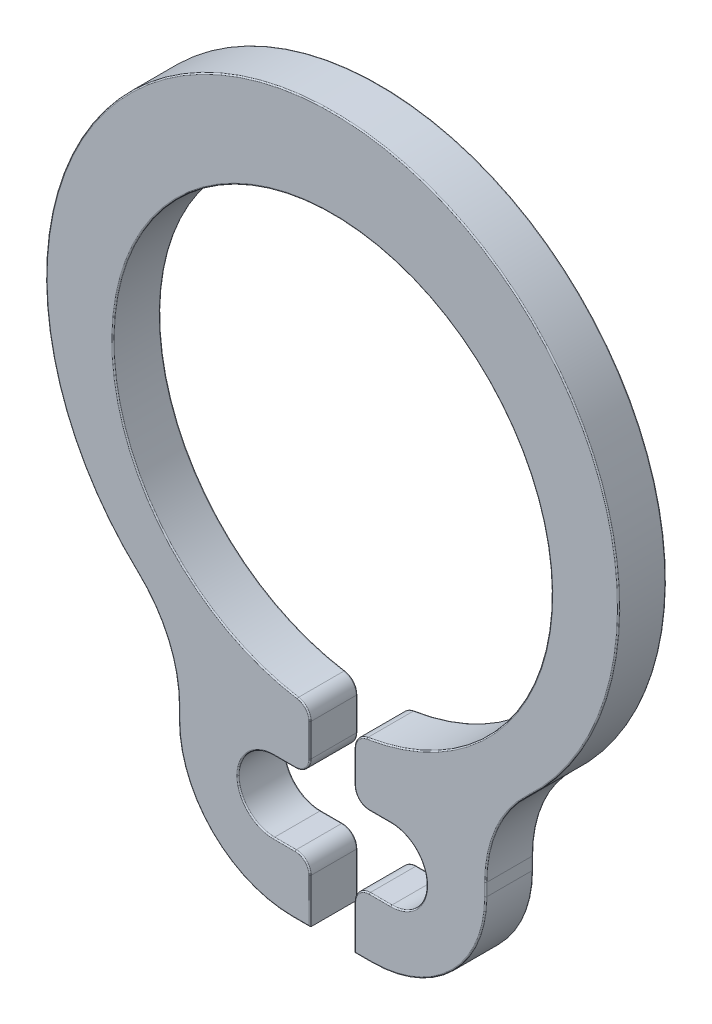
SolidWorks part; units mm, degrees
ref_plane "Front Plane" through (0, 0, 0) normal (0, 0, 1) x (1, 0, 0)
ref_plane "Top Plane" through (0, 0, 0) normal (0, 1, 0) x (1, 0, 0)
ref_plane "Right Plane" through (0, 0, 0) normal (1, 0, 0) x (0, 0, -1)
sketch "Sketch1" plane through (0, 0, 0) normal (0, 0, 1) x (1, 0, 0)
  line L0 (0, 6.05) -> (0, -6.05) construction
  line L1 (-0.99, -4.45) -> (0.99, -4.45) construction
  line L2 (-0.99, -3.85) -> (0.99, -3.85)
  line L3 (-0.99, -5.05) -> (0.99, -5.05)
  line L4 (1.59, -4.45) -> (2.59, -4.45) construction
  line L5 (0, -2.85) -> (0, -3.85) construction
  circle A0 centre (0, 0.85) radius 3.7
  arc A3 (-0.99, -3.85) -> (-0.99, -5.05) centre (-0.99, -4.45) ccw
  arc A4 (0.99, -5.05) -> (0.99, -3.85) centre (0.99, -4.45) ccw
  circle A5 centre (0, 1.22) radius 4.83 construction
  circle A6 centre (0, 0.85) radius 4 construction
  circle A7 centre (0, 0.85) radius 3.8 construction
  point P6 (0, 4.55)
  point P7 (0, -2.85)
  point P10 (0, -4.45)
  dimension "For OD" = 8
  dimension "ID" = 7.4
  dimension "Band Width" = 1.5
  dimension "Tap Height" = 3.2
  dimension "Tap ID" = 1.2
  dimension "D3" = 1.6
  dimension "Tap Width Ref" = 5.18
  dimension "D1" = 0.37
sketch "Sketch2" plane through (0, 0, 0) normal (1, 0, 0) x (0, 0, -1)
  line L0 (-0.4, 6.05) -> (0.4, 6.05) construction
  line L1 (0, 7.75) -> (0, -6.05) construction
  line L2 (0, 6.05) -> (0, -6.05) construction
  line L3 (-0.45, 7.75) -> (0.45, 7.75) construction
  line L4 (-0.45, -6.05) -> (0.45, -6.05) construction
  dimension "Thickness" = 0.8
  dimension "For Groove Width" = 0.9
sketch "Sketch3" plane through (0, 0, 0) normal (0, 0, 1) x (1, 0, 0)
  line L0 (-0.99, -5.05) -> (0.99, -5.05) construction
  line L1 (-0.99, -3.85) -> (0.99, -3.85) construction
  line L2 (-0.99, -5.05) -> (0.99, -5.05)
  line L3 (-0.99, -3.85) -> (0.99, -3.85)
  line L4 (2.59, -3.9186) -> (2.59, -4.13)
  line L5 (-0.67, -6.05) -> (0.67, -6.05)
  line L6 (-2.59, -3.9186) -> (-2.59, -4.13)
  line L7 (-1.59, -4.45) -> (-2.59, -4.45) construction
  line L8 (1.59, -4.45) -> (2.59, -4.45) construction
  arc A0 (-0.99, -3.85) -> (-0.99, -5.05) centre (-0.99, -4.45) ccw construction
  arc A1 (0.99, -5.05) -> (0.99, -3.85) centre (0.99, -4.45) ccw construction
  arc A2 (-0.99, -3.85) -> (-0.99, -5.05) centre (-0.99, -4.45) ccw
  arc A3 (0.99, -5.05) -> (0.99, -3.85) centre (0.99, -4.45) ccw
  circle A4 centre (0, 0.85) radius 3.7 construction
  circle A5 centre (0, 0.85) radius 3.7
  arc A6 (-3.2875, -2.3186) -> (3.2875, -2.3186) centre (0, 1.22) cw
  arc A8 (3.2875, -2.3186) -> (2.59, -3.9186) centre (4.7739, -3.9186) ccw
  arc A9 (2.59, -4.13) -> (0.67, -6.05) centre (0.67, -4.13) cw
  arc A10 (-3.2875, -2.3186) -> (-2.59, -3.9186) centre (-4.7739, -3.9186) cw
  arc A11 (-2.59, -4.13) -> (-0.67, -6.05) centre (-0.67, -4.13) ccw
  circle A12 centre (0, 1.22) radius 4.83 construction
  dimension "D1" = 1.6
  dimension "D2" = 1.92
  dimension "D3" = 1
extrude "Boss-Extrude1" add sketch "Sketch3" along normal mid plane 0.8
sketch "Sketch4" plane through (0, 0, 0) normal (0, 0, 1) x (1, 0, 0)
  line L0 (0, 0.85) -> (0, -6.05)
extrude "Cut-Extrude-Thin1" cut sketch "Sketch4" against normal through all both and the other way through all thin thin type mid plane wall 0.75
fillet "Fillet2" radius 0.25 6 edges at (0.375, -5.05, 0) (-0.375, -5.05, 0) (0.375, -3.85, 0) (0.375, -2.8309, 0) (-0.375, -3.85, 0) (-0.375, -2.8309, 0)
fillet "Fillet1" radius 0.02 52 edges at (-0.8075, -5.05, -0.4) (-1.59, -4.45, -0.4) (-0.8075, -3.85, -0.4) (0, 4.55, -0.4) (0.8075, -3.85, -0.4) (1.59, -4.45, -0.4) (0.8075, -5.05, -0.4) (0.375, -5.675, -0.4) (0.5225, -6.05, -0.4) (2.0276, -5.4876, -0.4) (2.59, -4.0243, -0.4) (2.7719, -3.0459, -0.4) (0, 6.05, -0.4) (-2.7719, -3.0459, -0.4) (-2.59, -4.0243, -0.4) (-2.0276, -5.4876, -0.4) (-0.5225, -6.05, -0.4) (-0.375, -5.675, -0.4) (-2.0276, -5.4876, 0.4) (-2.59, -4.0243, 0.4) (-2.7719, -3.0459, 0.4) (0, 6.05, 0.4) (2.7719, -3.0459, 0.4) (2.59, -4.0243, 0.4) (2.0276, -5.4876, 0.4) (0.5225, -6.05, 0.4) (0.375, -5.675, 0.4) (0.8075, -5.05, 0.4) (1.59, -4.45, 0.4) (0.8075, -3.85, 0.4) (0, 4.55, 0.4) (-0.8075, -3.85, 0.4) (-1.59, -4.45, 0.4) (-0.8075, -5.05, 0.4) (-0.375, -5.675, 0.4) (-0.5225, -6.05, 0.4) (-0.4482, -5.1232, -0.4) (-0.4482, -3.7768, -0.4) (-0.375, -3.3251, -0.4) (-0.4348, -2.8881, -0.4) (0.4348, -2.8881, -0.4) (0.375, -3.3251, -0.4) (0.4482, -3.7768, -0.4) (0.4482, -5.1232, -0.4) (0.4482, -3.7768, 0.4) (0.375, -3.3251, 0.4) (0.4348, -2.8881, 0.4) (-0.4348, -2.8881, 0.4) (-0.375, -3.3251, 0.4) (-0.4482, -3.7768, 0.4) (-0.4482, -5.1232, 0.4) (0.4482, -5.1232, 0.4)
ref_axis "Z" through (0, 0.85, 0.38) along (0, 0, -1)
equation "\"D3@Sketch1\"=\"Tap Height@Sketch1\"*0.5"
equation "\"D1@Sketch3\"=\"Tap Height@Sketch1\"*0.5"
equation "\"D2@Sketch3\"=\"Tap Height@Sketch1\"*0.6"
equation "\"D1@Boss-Extrude1\" = \"Thickness@Sketch2\""
equation "\"D1@Sketch1\"= \"ID@Sketch1\" * 0.05"
equation "\"D1@Fillet2\"=\"D3@Sketch3\"*0.25"
